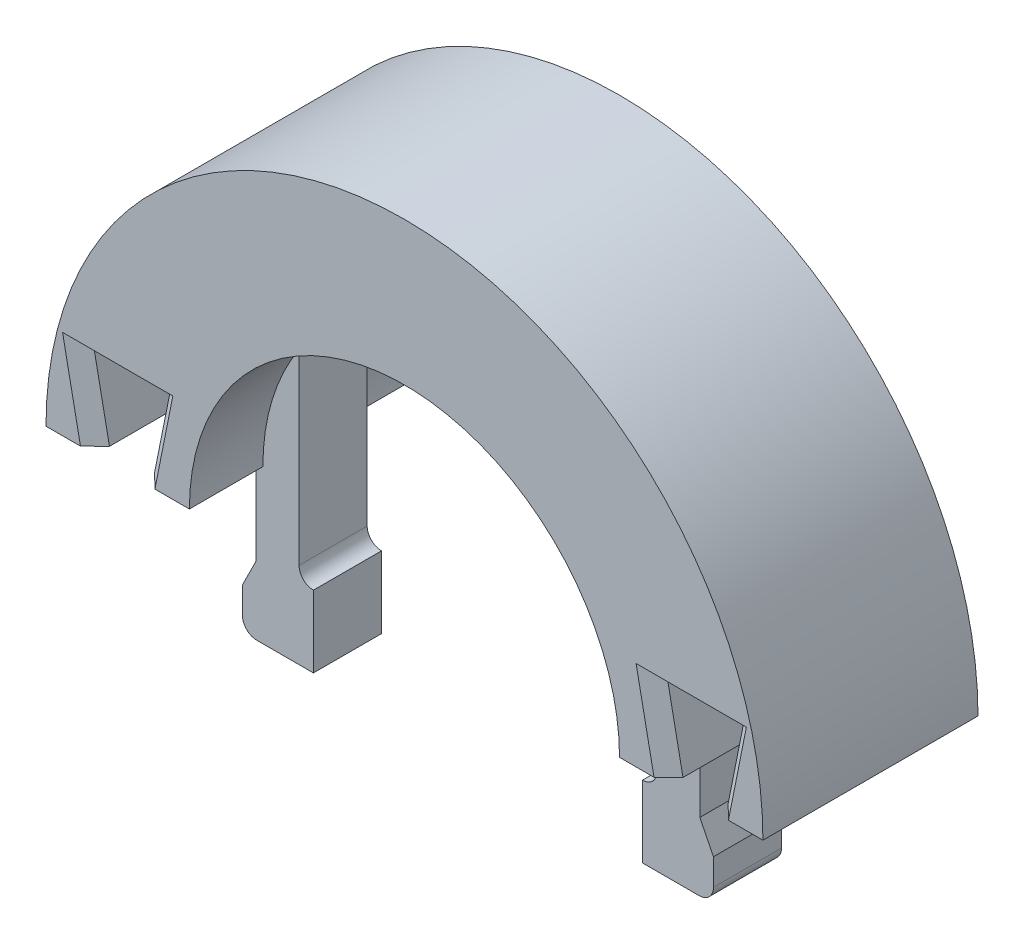
SolidWorks part; units mm, degrees
ref_plane "Front Plane" through (0, 0, 0) normal (0, 0, 1) x (1, 0, 0)
ref_plane "Top Plane" through (0, 0, 0) normal (0, 1, 0) x (1, 0, 0)
ref_plane "Right Plane" through (0, 0, 0) normal (1, 0, 0) x (0, 0, -1)
sketch "Sketch1" plane through (0, 0, 0) normal (0, 0, 1) x (1, 0, 0)
  line L0 (0, 0) -> (49.1339, 0) construction
  line L1 (49.1339, 0) -> (-47.428, 0) construction
  line L2 (-25, 0) -> (-15, 0)
  line L3 (15, 0) -> (25, 0)
  arc A0 (15, 0) -> (-15, 0) centre (0, 0) ccw
  arc A1 (25, 0) -> (-25, 0) centre (0, 0) ccw
  dimension "D1" = 50
  dimension "D2" = 30
extrude "Boss-Extrude1" add sketch "Sketch1" along normal mid plane 15 contours A1 L2 A0 L3
ref_plane "Plane1" through (0, 0, 7.5) normal (0, 0, 1) x (1, 0, 0)
sketch "Sketch2" plane through (0, 0, 7.5) normal (0, 0, 1) x (1, 0, 0)
  line L0 (-20, 0) -> (-20, -50000) construction
  line L1 (-25, 0) -> (-15, 0) construction
  line L2 (-22.625, 0) -> (-22.625, -50000) construction
  line L3 (-17.375, 0) -> (-17.375, -50000) construction
  line L4 (-22.625, 5.25) -> (-17.375, 5.25)
  line L5 (-22.625, 5.25) -> (-21.575, 0)
  line L6 (-21.575, 0) -> (-18.425, 0)
  line L7 (-18.425, 0) -> (-17.375, 5.25)
  point P4 (-20, 0)
  dimension "D1" = 2.625
  dimension "D2" = 2.625
  dimension "D3" = 5.25
  dimension "D4" = 1.575
  dimension "D5" = 1.575
extrude "Cut-Extrude1" cut sketch "Sketch2" against normal through all contours L4 L7 L6 L5
mirror "Mirror1" about plane through (0, 0, 0) normal (1, 0, 0) of "Cut-Extrude1"
ref_plane "Plane2" through (0, 0, 0) normal (0, 0, 1) x (1, 0, 0)
sketch "Sketch3" plane through (0, 0, 0) normal (0, 0, 1) x (1, 0, 0)
  line L1 (12.5557, 34.0493) -> (16.1731, 34.0493)
  line L2 (12.475, 8.3291) -> (12.475, -5.7)
  line L4 (15.475, 0) -> (15.475, -5.95)
  line L5 (25, 0) -> (-25, 0) construction
  line L6 (11.475, -8) -> (12.475, -8) construction
  line L7 (8.25, 0) -> (-8.25, 0) construction
  line L8 (15.475, 0) -> (15, 0)
  line L10 (11.475, -10.7) -> (16.425, -10.7)
  line L11 (11.475, -10.7) -> (11.475, -5.7)
  line L12 (11.475, -5.7) -> (12.475, -5.7)
  line L13 (16.425, -10.7) -> (16.425, -7.85)
  line L14 (-985.4422, -8) -> (-12.7136, -8) construction
  line L15 (16.425, -7.85) -> (15.475, -5.95)
  arc A0 (15, 0) -> (-15, 0) centre (0, 0) ccw construction
  arc A2 (15, 0) -> (12.475, 8.3291) centre (0, 0) ccw
  arc A3 (25, 0) -> (-25, 0) centre (0, 0) ccw construction
  point P11 (14, -14.04)
  point P23 (0, 0)
  point P24 (0, 0)
  dimension "D1" = 5
  dimension "D2" = 5.7
  dimension "D3" = 1
  dimension "D4" = 0.475
  dimension "D5" = 3
  dimension "D6" = 1.425
  dimension "D7" = 1.9
  dimension "D8" = 2.85
extrude "Boss-Extrude3" add sketch "Sketch3" along normal mid plane 4.75 contours L10 L13 L15 L4 L8 A2 L2 L12 L11
mirror "Mirror11" about plane through (0, 0, 0) normal (1, 0, 0) of "Boss-Extrude3"
fillet "Fillet1" radius 1 1 edges at (16.425, -10.7, 0)
fillet "Fillet2" radius 1 1 edges at (-16.425, -10.7, 0)
fillet "Fillet3" radius 1 1 edges at (-12.475, -5.7, 0)
fillet "Fillet4" radius 1 1 edges at (12.475, -5.7, 0)
chamfer "Chamfer1" distance 1 angle 45 3 edges at (-17.9, 2.625, 7.5) (-22.1, 2.625, 7.5) (-20, 5.25, 7.5)
chamfer "Chamfer2" distance 1 angle 45 3 edges at (17.9, 2.625, 7.5) (20, 5.25, 7.5) (22.1, 2.625, 7.5)
